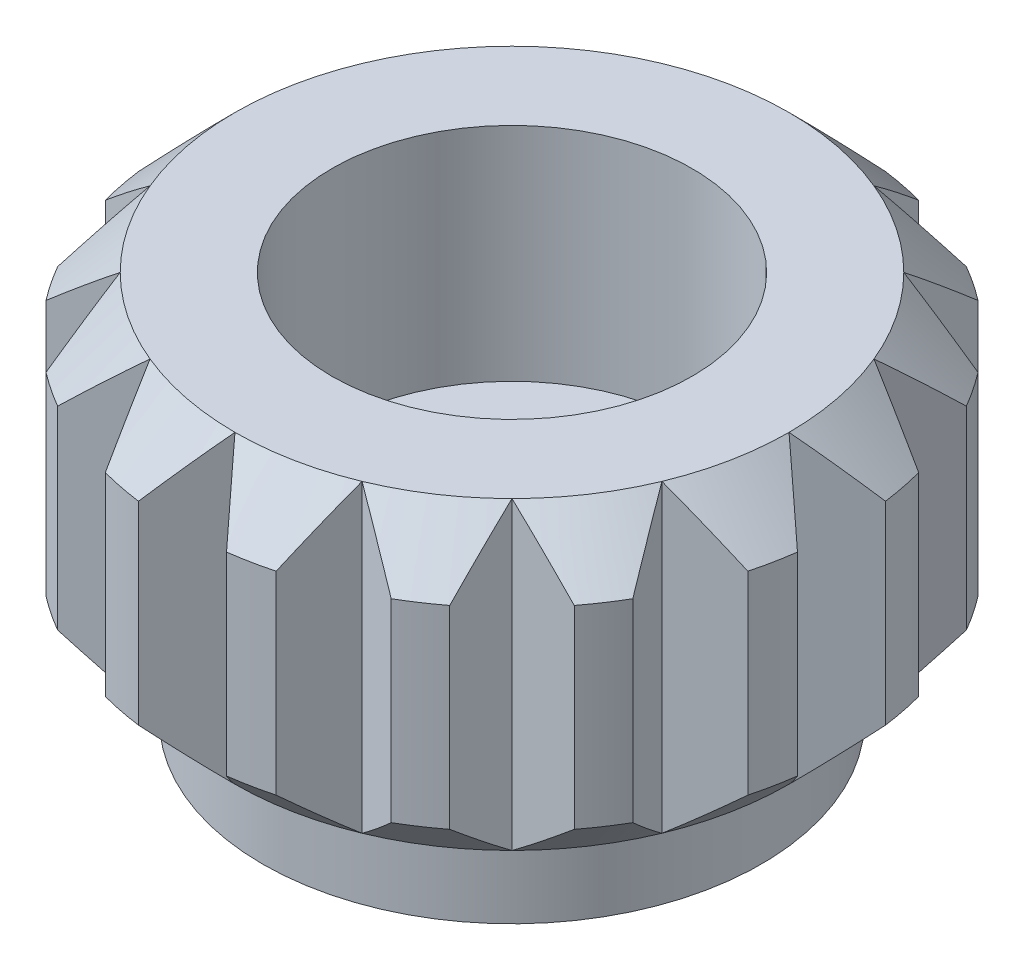
SolidWorks part; units mm, degrees
ref_plane "Plan de face" through (0, 0, 0) normal (0, 0, 1) x (1, 0, 0)
ref_plane "Plan de dessus" through (0, 0, 0) normal (0, 1, 0) x (1, 0, 0)
ref_plane "Plan de droite" through (0, 0, 0) normal (1, 0, 0) x (0, 0, -1)
sketch "Esquisse1" plane through (0, 0, 0) normal (0, 1, 0) x (1, 0, 0)
  circle A0 centre (0, 0) radius 6
  dimension "D1" = 12
extrude "Boss.-Extru.1" add sketch "Esquisse1" along normal blind 7
sketch "Esquisse2" plane through (0, 0, 0) normal (0, -1, 0) x (1, 0, 0)
  circle A2 centre (0, 0) radius 4.5
  circle A3 centre (0, 0) radius 4.5
  dimension "D1" = 1.5
extrude "Enlèv. mat.-Extru.1" cut sketch "Esquisse2" against normal blind 1.5 flip side to cut
chamfer "Chanfrein1" distance 1 angle 45 2 edges at (0, 7, 6) (0, 1.5, -6)
hole_wizard "Chambrage pour vis à tête cylindrique à 6 pans creux (ou vis CHC) M31" positions "Esquisse3" profile "Esquisse4" counterbore size "M3" standard "Ansi Metric" end condition through all
sketch "Esquisse3" plane through (0, 7, 0) normal (0, 1, 0) x (1, 0, 0)
  point P0 (0, 0)
sketch "Esquisse4" plane through (0, 7, 0) normal (1, 0, 0) x (0, 0, 1)
  line L0 (0, 0) -> (0, 7)
  line L1 (0, 7) -> (1.6, 7)
  line L3 (1.6, 7) -> (1.6, 4)
  line L4 (1.6, 4) -> (3.25, 4)
  line L5 (3.25, 4) -> (3.25, 0)
  line L7 (3.25, 0) -> (0, 0)
  line L11 (0, -6.35) -> (0, 107.95) construction
  dimension "Diamètre du perçage jusqu'au prochain" = 3.2
  dimension "Profondeur du perçage jusqu'au prochain" = 7
  dimension "Diamètre du chambrage" = 6.5
  dimension "Profondeur du chambrage" = 4
sketch "Esquisse5" plane through (0, 7, 0) normal (0, 1, 0) x (1, 0, 0)
  line L0 (-5, 0) -> (-6.6456, 1.3809)
  line L1 (-6.6456, 1.3809) -> (-6.6456, -1.3809)
  line L2 (-6.6456, -1.3809) -> (-5, 0)
  line L3 (-6.6456, 0) -> (0, 0) construction
  circle A0 centre (0, 0) radius 5 construction
  dimension "D1" = 80
extrude "Enlèv. mat.-Extru.2" cut sketch "Esquisse5" against normal through all
pattern_circular "Répétition circulaire1" count 16 over 360 about axis through (0, 7, 0) along (0, 1, 0) of "Enlèv. mat.-Extru.2"
